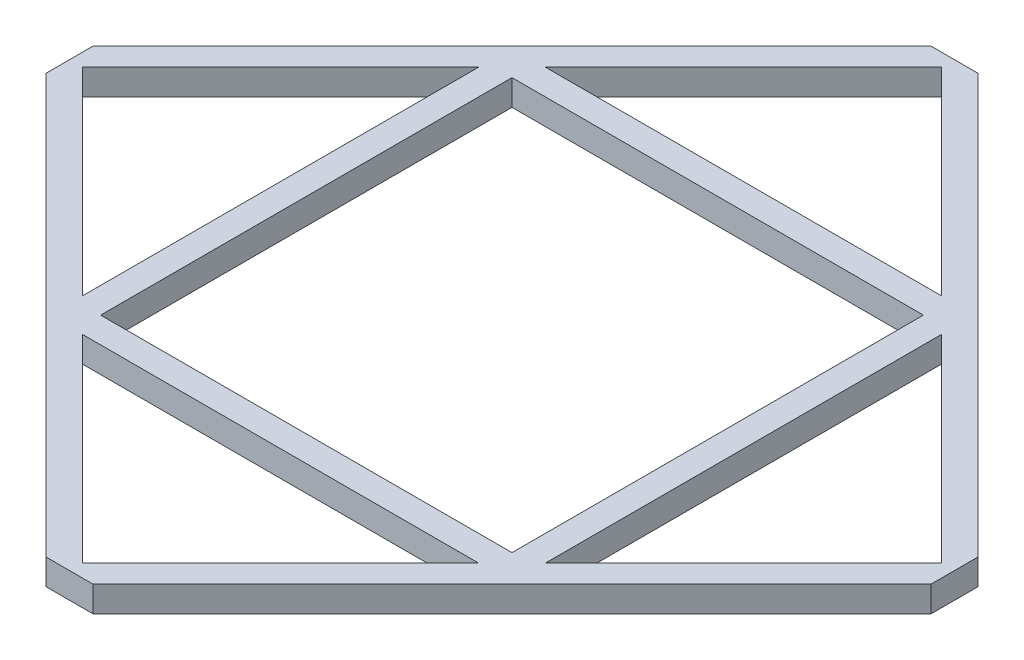
SolidWorks part; units mm, degrees
ref_plane "Front Plane" through (0, 0, 0) normal (0, 0, 1) x (1, 0, 0)
ref_plane "Top Plane" through (0, 0, 0) normal (0, 1, 0) x (1, 0, 0)
ref_plane "Right Plane" through (0, 0, 0) normal (1, 0, 0) x (0, 0, -1)
sketch "Sketch2" plane through (0, 0, 0) normal (0, 1, 0) x (1, 0, 0)
  line L1 (-6871, 6871) -> (-365.6854, 6871) construction
  line L2 (-6871, 6871) -> (-6871, -6871) construction
  line L3 (-6871, -6871) -> (6871, -6871) construction
  line L4 (6871, 6871) -> (6871, -6871) construction
  line L5 (-6871, 6871) -> (6871, -6871) construction
  line L6 (-6871, -6871) -> (6871, 6871) construction
  line L20 (0, -6871) -> (0, 6871) construction
  line L21 (-6871, 0) -> (6871, 0) construction
  line L42 (0, -6671) -> (-3076.9214, -3594.0786)
  line L43 (0, -6671) -> (3076.9214, -3594.0786)
  line L49 (-6671, 0) -> (-3594.0786, 3076.9214)
  line L52 (6671, 0) -> (3594.0786, 3076.9214)
  line L54 (0, -6671) -> (0, 6671) construction
  line L56 (-6671, 0) -> (6671, 0) construction
  line L58 (-6871, 365.6854) -> (-365.6854, 6871)
  line L59 (6871, 365.6854) -> (365.6854, 6871)
  line L60 (365.6854, -6871) -> (6871, -365.6854)
  line L64 (-365.6854, -6871) -> (-6871, -365.6854)
  line L66 (-3076.9214, 3594.0786) -> (3076.9214, 3594.0786)
  line L67 (-3194.0786, -3194.0786) -> (3194.0786, -3194.0786)
  line L71 (-3194.0786, -3194.0786) -> (-3194.0786, 3194.0786)
  line L72 (-3194.0786, 3194.0786) -> (3194.0786, 3194.0786)
  line L75 (0, -7236.6854) -> (7236.6854, 0) construction
  line L76 (3194.0786, -3194.0786) -> (3194.0786, 3194.0786)
  line L77 (-3194.0786, -3194.0786) -> (3194.0786, 3194.0786) construction
  line L78 (-3194.0786, 3194.0786) -> (3194.0786, -3194.0786) construction
  line L79 (3594.0786, -3076.9214) -> (3594.0786, 3076.9214)
  line L80 (-3076.9214, -3594.0786) -> (3076.9214, -3594.0786)
  line L81 (-3594.0786, -3076.9214) -> (-3594.0786, 3076.9214)
  line L82 (3594.0786, -3594.0786) -> (3594.0786, 3594.0786) construction
  line L83 (-3594.0786, 3594.0786) -> (3594.0786, 3594.0786) construction
  line L84 (3076.9214, 3594.0786) -> (0, 6671)
  line L85 (6671, 0) -> (0, 6671) construction
  line L86 (-3594.0786, -3594.0786) -> (-3594.0786, 3594.0786) construction
  line L87 (-3076.9214, 3594.0786) -> (0, 6671)
  line L88 (-6671, 0) -> (0, 6671) construction
  line L89 (-3594.0786, -3594.0786) -> (3594.0786, -3594.0786) construction
  line L90 (-3594.0786, -3076.9214) -> (-6671, 0)
  line L91 (0, -6671) -> (-6671, 0) construction
  line L92 (3594.0786, -3076.9214) -> (6671, 0)
  line L93 (0, -6671) -> (6671, 0) construction
  line L94 (6871, 365.6854) -> (6871, -365.6854)
  line L95 (365.6854, 6871) -> (6871, 6871) construction
  line L96 (-365.6854, 6871) -> (365.6854, 6871)
  line L97 (7236.6854, 0) -> (0, 7236.6854) construction
  line L98 (-7236.6854, 0) -> (0, 7236.6854) construction
  line L99 (0, -7236.6854) -> (-7236.6854, 0) construction
  line L100 (-365.6854, -6871) -> (365.6854, -6871)
  line L101 (-6871, 365.6854) -> (-6871, -365.6854)
  point P0 (0, 0)
  point P5 (0, 0)
  dimension "D1" = 13742
  dimension "D2" = 200
  dimension "D3" = 400
  dimension "D4" = 200
  dimension "D5" = 400
extrude "Boss-Extrude1" add sketch "Sketch2" along normal blind 400 contours L58 L101 L64 L100 L60 L94 L59 L96 L81 L90 L49 L66 L87 L84 L42 L80 L43 L76 L67 L71 L72 L92 L79 L52 region at (-3480.9227, 0, -3480.9227)
